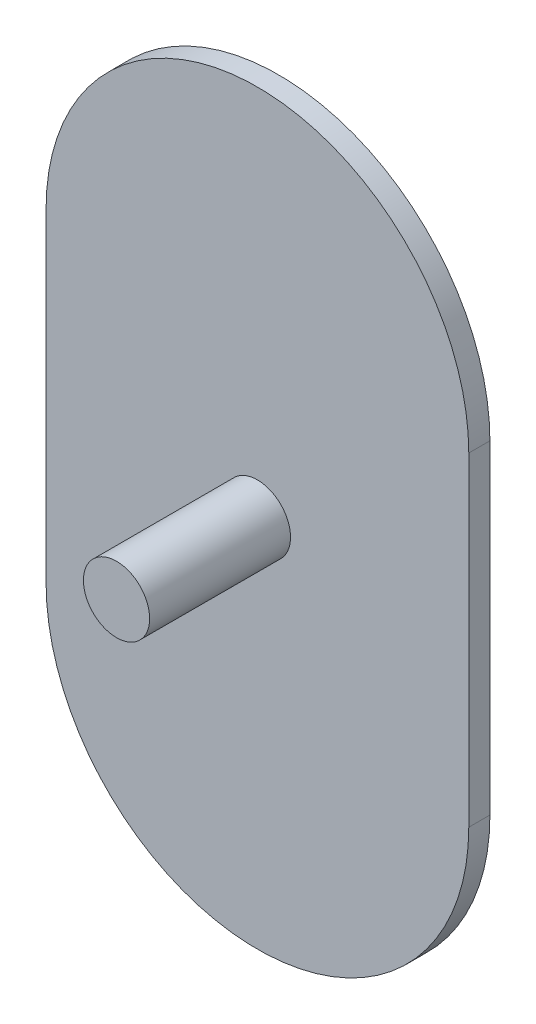
SolidWorks part; units mm, degrees
ref_plane "Płaszczyzna przednia" through (0, 0, 0) normal (0, 0, 1) x (1, 0, 0)
ref_plane "Płaszczyzna górna" through (0, 0, 0) normal (0, 1, 0) x (1, 0, 0)
ref_plane "Płaszczyzna prawa" through (0, 0, 0) normal (1, 0, 0) x (0, 0, -1)
sketch "Szkic33" plane through (0, 0, 0) normal (0, 0, 1) x (-1, 0, 0)
  line L0 (-44.5, 0) -> (45, 0) construction
  line L3 (0, 28.5) -> (0, -31.5) construction
  line L6 (-6, 12.5) -> (6, 12.5) construction
  line L9 (-6, 14.5) -> (6, 14.5)
  line L12 (-6, 10.5) -> (6, 10.5)
  line L13 (-6, -12.5) -> (6, -12.5) construction
  line L14 (-6, -14.5) -> (6, -14.5)
  line L15 (-6, -10.5) -> (6, -10.5)
  line L16 (-59.081, 0) -> (59.081, 0) construction
  circle A0 centre (0, 12.5) radius 4
  circle A4 centre (0, -12.5) radius 4
  arc A7 (-6, 14.5) -> (-6, 10.5) centre (-6, 12.5) ccw
  arc A8 (6, 10.5) -> (6, 14.5) centre (6, 12.5) ccw
  arc A9 (-6, -14.5) -> (-6, -10.5) centre (-6, -12.5) cw
  arc A10 (6, -10.5) -> (6, -14.5) centre (6, -12.5) cw
  point P14 (0, 12.5)
  point P26 (0, -12.5)
  point P34 (0, 0)
  dimension "D1" = 8
  dimension "D2" = 12.5
  dimension "D3" = 4
  dimension "D4" = 6
sketch "Szkic34" plane through (0, 0, 0) normal (0, 0, 1) x (1, 0, 0)
  line L12 (-47, 26.5) -> (-47, -26.5)
  line L13 (-43, -30.5) -> (43, -30.5)
  line L14 (47, -26.5) -> (47, 26.5)
  line L15 (43, 30.5) -> (-43, 30.5)
  spline S4 degree 3 poles (-43, 30.5) (-45.3431, 30.5) (-47, 28.8431) (-47, 26.5) knots 0 0 0 0 1 1 1 1 weights 1 0.804738 0.804738 1
  spline S5 degree 3 poles (-47, -26.5) (-47, -28.8431) (-45.3431, -30.5) (-43, -30.5) knots 0 0 0 0 1 1 1 1 weights 1 0.804738 0.804738 1
  spline S6 degree 3 poles (43, -30.5) (45.3431, -30.5) (47, -28.8431) (47, -26.5) knots 0 0 0 0 1 1 1 1 weights 1 0.804738 0.804738 1
  spline S7 degree 3 poles (47, 26.5) (47, 28.8431) (45.3431, 30.5) (43, 30.5) knots 0 0 0 0 1 1 1 1 weights 1 0.804738 0.804738 1
sketch "Szkic35" plane through (0, 0, 0) normal (0, 0, 1) x (1, 0, 0)
  line L0 (-15, -11.5) -> (-15, 11.5)
  line L1 (0, 16.5) -> (-15, 16.5) construction
  line L2 (0, 16.5) -> (15, 16.5) construction
  line L3 (22.2734, -16.5) -> (7.2734, -16.5) construction
  line L4 (22.2734, -16.5) -> (15, -16.5) construction
  line L5 (15, 11.5) -> (15, -11.5)
  line L8 (0, 26.5) -> (0, -26.5) construction
  line L9 (-15, 0) -> (15, 0) construction
  circle A0 centre (0, -12.5) radius 4 construction
  circle A1 centre (0, 12.5) radius 4 construction
  arc A2 (-15, 11.5) -> (15, 11.5) centre (0, 11.5) cw
  arc A3 (-15, -11.5) -> (15, -11.5) centre (0, -11.5) ccw
  circle A4 centre (0, 0) radius 2.5 construction
  dimension "D6" = 1
  dimension "D7" = 1
  dimension "D8" = 5
  dimension "D1" = 15
  dimension "D2" = 15
  dimension "D3" = 5
  dimension "D4" = 5
  dimension "D5" = 15
  dimension "D9" = 15
extrude "Dodanie-wyciągnięcie2" add sketch "Szkic35" along normal blind 1.5
sketch "Szkic37" plane through (0, 0, 0) normal (0, 0, -1) x (-1, 0, 0)
  circle A0 centre (0, 12.5) radius 1.85
  circle A1 centre (0, -12.5) radius 1.85
  dimension "D1" = 3.7
  dimension "D2" = 2
extrude "Dodanie-wyciągnięcie3" add sketch "Szkic37" along normal blind 1.5
sketch "Szkic38" plane through (0, 0, -1.5) normal (0, 0, -1) x (-1, 0, 0)
  circle A0 centre (0, 12.5) radius 3.85
  circle A1 centre (0, -12.5) radius 3.85
  dimension "D1" = 7.7
  dimension "D2" = 2
extrude "Dodanie-wyciągnięcie4" add sketch "Szkic38" along normal blind 1.7
fillet "Zaokrąglenie1" radius 2 2 edges at (-3.85, -12.5, -3.2) (-3.85, 12.5, -3.2)
sketch "Szkic39" plane through (0, 0, 1.5) normal (0, 0, 1) x (1, 0, 0)
  circle A0 centre (0, 0) radius 2.35
  circle A2 centre (0, 0) radius 2.5 construction
  point P3 (0, 0)
  point P6 (0, 0)
  point P7 (0, 0)
  dimension "D1" = 4.7
  dimension "D2" = 4.7
extrude "Dodanie-wyciągnięcie5" add sketch "Szkic39" along normal blind 10
